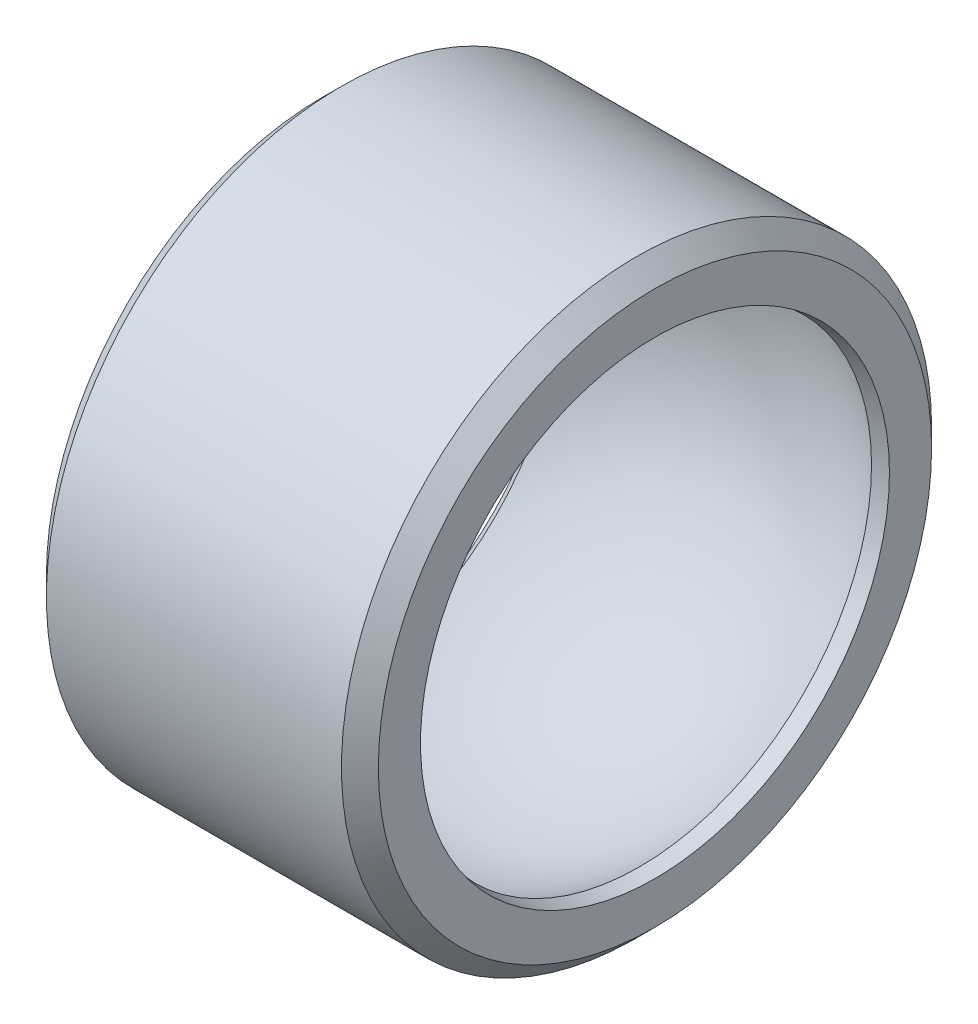
SolidWorks part; units mm, degrees
material "Латунь"
ref_plane "Front Plane" through (0, 0, 0) normal (0, 0, 1) x (1, 0, 0)
ref_plane "Top Plane" through (0, 0, 0) normal (0, 1, 0) x (1, 0, 0)
ref_plane "Right Plane" through (0, 0, 0) normal (1, 0, 0) x (0, 0, -1)
sketch "Эскиз1" plane through (0, 0, 0) normal (1, 0, 0) x (0, 0, -1)
  circle A0 centre (0, 0) radius 8
  dimension "D1" = 16
extrude "Бобышка-Вытянуть1" add sketch "Эскиз1" along normal blind 9
sketch "Эскиз2" plane through (0, 0, 0) normal (0, 0, 1) x (1, 0, 0)
  line L0 (0, 0) -> (9, 0) construction
  line L1 (9, -8) -> (9, 8) construction
  line L2 (-3, 0) -> (12, 0)
  circle A0 centre (4.5, 0) radius 7.5 construction
  arc A1 (-3, 0) -> (12, 0) centre (4.5, 0) cw
  dimension "D1" = 15
revolve "Вырез-Повернуть1" cut sketch "Эскиз2" angle 360 about L0
chamfer "Фаска1" distance 0.5 angle 45 2 edges at (9, 0, -6) (0, 0, -6) first distance on face at (9, 0, -6) first distance on face at (0, 0, -6)
chamfer "Фаска2" distance 0.5 angle 45 2 edges at (9, 0, -8) (0, 0, -8)
